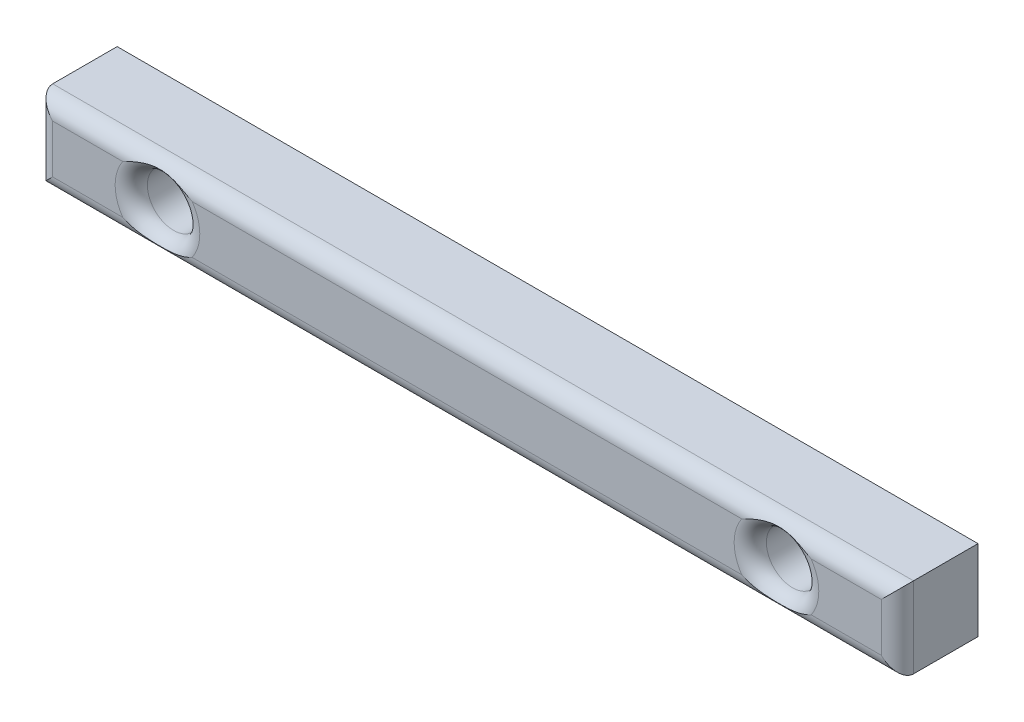
SolidWorks part; units mm, degrees
ref_plane "Front Plane" through (0, 0, 0) normal (0, 0, 1) x (1, 0, 0)
ref_plane "Top Plane" through (0, 0, 0) normal (0, 1, 0) x (1, 0, 0)
ref_plane "Right Plane" through (0, 0, 0) normal (1, 0, 0) x (0, 0, -1)
sketch "Sketch1" plane through (0, 0, 0) normal (0, 0, 1) x (1, 0, 0)
  line L1 (0, 0) -> (106.79, 0)
  line L2 (0, 0) -> (0, -10)
  line L3 (0, -10) -> (106.79, -10)
  line L4 (106.79, 0) -> (106.79, -10)
  line L5 (0, 0) -> (106.79, -10) construction
  line L6 (0, -10) -> (106.79, 0) construction
  point P4 (53.395, -5)
  dimension "D1" = 10
  dimension "D2" = 106.79
extrude "Boss-Extrude1" add sketch "Sketch1" along normal blind 10
sketch "Sketch2" plane through (0, 0, 10) normal (0, 0, 1) x (1, 0, 0)
  line L0 (0, -5) -> (15, -5) construction
  line L1 (0, 0) -> (0, -10) construction
  line L2 (15, -5) -> (91.79, -5) construction
  line L3 (91.79, -5) -> (106.79, -5) construction
  line L4 (106.79, -10) -> (106.79, 0) construction
  circle A0 centre (15, -5) radius 2
  circle A1 centre (91.79, -5) radius 2
  dimension "D3" = 4
  dimension "D4" = 4
  dimension "D1" = 15
  dimension "D2" = 15
extrude "Cut-Extrude1" cut sketch "Sketch2" against normal blind 10
sketch "Sketch3" plane through (0, 0, 10) normal (0, 0, 1) x (1, 0, 0)
  circle A0 centre (15, -5) radius 3.25
  circle A1 centre (91.79, -5) radius 3.25
  dimension "D1" = 6.5
  dimension "D2" = 6.5
extrude "Cut-Extrude2" cut sketch "Sketch3" against normal blind 7
fillet "Fillet1" radius 2 6 edges at (53.395, 0, 10) (106.79, -5, 10) (53.395, -10, 10) (0, -5, 10) (95.04, -5, 10) (18.25, -5, 10)
